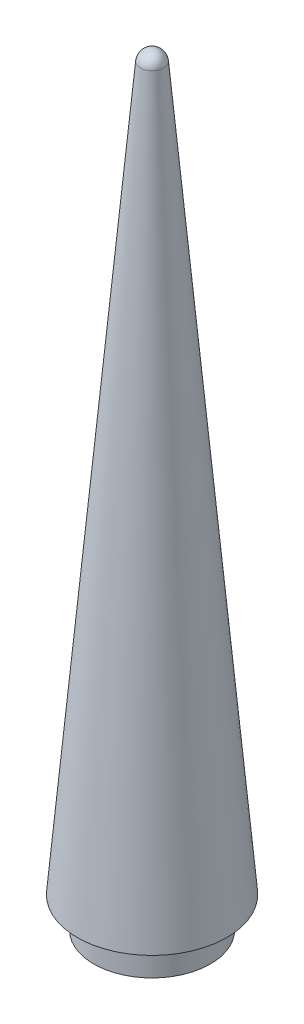
SolidWorks part; units mm, degrees
material "6061 Alloy"
ref_plane "Front Plane" through (0, 0, 0) normal (0, 0, 1) x (1, 0, 0)
ref_plane "Top Plane" through (0, 0, 0) normal (0, 1, 0) x (1, 0, 0)
ref_plane "Right Plane" through (0, 0, 0) normal (1, 0, 0) x (0, 0, -1)
sketch "Sketch2" plane through (0, 0, 0) normal (0, 0, 1) x (1, 0, 0)
  line L0 (0, 2.1015) -> (0, 141.5732)
  line L1 (0, 141.5732) -> (12.2022, 2.1015)
  line L2 (12.2022, 2.1015) -> (9.525, 2.1015)
  line L3 (9.525, 2.1015) -> (9.525, -2.9785)
  line L4 (9.525, -2.9785) -> (0, -2.9785)
  line L5 (0, -2.9785) -> (0, 2.1015)
  line L6 (0, 121.6208) -> (-2.1023, 121.6208) construction
  line L7 (0, -200166.8953) -> (0, 200141.5732) construction
  line L8 (12.2022, 2.1015) -> (-12.2022, 2.1015) construction
  line L9 (0, 141.5732) -> (26.9875, -166.8953) construction
  arc A0 (1.8978, 119.8818) -> (0, 121.6208) centre (0, 119.7158) ccw
revolve "Revolve1" add sketch "Sketch2" angle 360 about L0 region at (4.1764, 44.2733, 0)
sketch "Sketch3" plane through (0, -2.9785, 0) normal (0, -1, 0) x (1, 0, 0)
  point P0 (0, 0)
hole_wizard "1/4-20 Tapped Hole1" positions "Sketch3" profile "Sketch4" tap size "1/4-20" standard "ANSI Inch"
sketch "Sketch4" plane through (0, -2.9785, 0) normal (1, 0, 0) x (0, 0, -1)
  line L0 (0, 0) -> (0, 65.0338)
  line L1 (0, 65.0338) -> (2.5527, 63.5)
  line L2 (2.5527, 63.5) -> (2.5527, 1.2573)
  line L3 (2.5527, 1.2573) -> (3.81, 0)
  line L5 (3.81, 0) -> (0, 0)
  line L6 (-2.5527, 1.2573) -> (-3.81, 0) construction
  line L10 (0, 65.0338) -> (-2.5527, 63.5) construction
  line L11 (0, -6.35) -> (0, 107.95) construction
  dimension "Tap Drill Dia." = 5.1054
  dimension "Tap Drill Depth" = 63.5
  dimension "Near C'Sink Dia." = 7.62
  dimension "Near C'Sink Angle" = 90
  dimension "Drill Angle" = 118
cosmetic thread "Hole Thread1" parameters "D1"=50.8, "D2"=6.35
